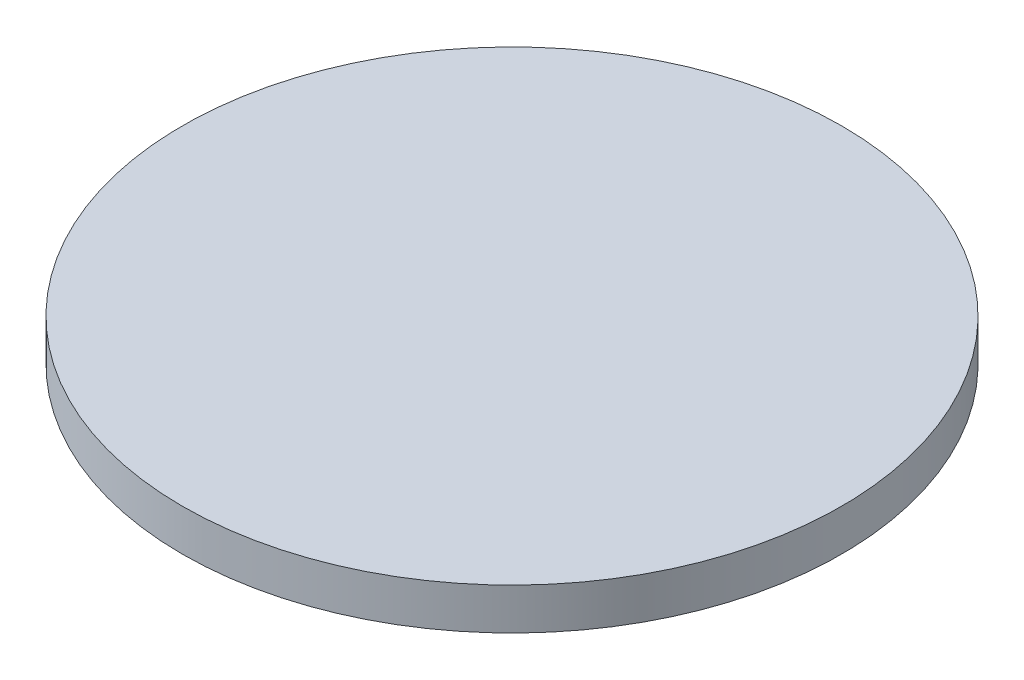
SolidWorks part; units mm, degrees
material "1060 Alloy"
ref_plane "Front Plane" through (0, 0, 0) normal (0, 0, 1) x (1, 0, 0)
ref_plane "Top Plane" through (0, 0, 0) normal (0, 1, 0) x (1, 0, 0)
ref_plane "Right Plane" through (0, 0, 0) normal (1, 0, 0) x (0, 0, -1)
sketch "Sketch1" plane through (0, 0, 0) normal (0, 1, 0) x (1, 0, 0)
  circle A0 centre (0, 0) radius 15.875
  dimension "D1" = 31.75
extrude "Boss-Extrude1" add sketch "Sketch1" along normal blind 1
sketch "Sketch6" plane through (0, 0, 0) normal (0, -1, 0) x (1, 0, 0)
  circle A0 centre (0, 0) radius 15.875
  circle A1 centre (0, 0) radius 9.525
  circle A2 centre (0, 0) radius 15.875 construction
  dimension "D1" = 0
  dimension "D2" = 19.05
extrude "Boss-Extrude3" add sketch "Sketch6" along normal blind 1
thread "Thread1" pitch 0.25 method cut profile "Thread Profile1" start angle 0, offset 0, length 1, pitch 0.25, diameter 19.05
ref_plane "Plane1" through (9.525, -1, 0) normal (0, 0, 1) x (1, 0, 0)
sketch "Thread Profile1" plane through (9.525, -1, 0) normal (0, 0, 1) x (1, 0, 0)
  line L0 (0, 0) -> (0, 0.25) construction
  line L1 (0, 0) -> (0.1353, 0.0781)
  line L2 (0.1353, 0.0781) -> (0.1353, 0.1094)
  line L3 (0.1353, 0.1094) -> (0, 0.1875)
  line L4 (0.1353, 0.0937) -> (0, 0.0937) construction
  line L11 (0, 0) -> (0, 0.1875)
  point P2 (0, 0)
  dimension "Pitch" = 0.25
  dimension "Profile_Angle" = 60
  dimension "Profile_Land" = 0.0312
  dimension "Profile_Height" = 0.1353
